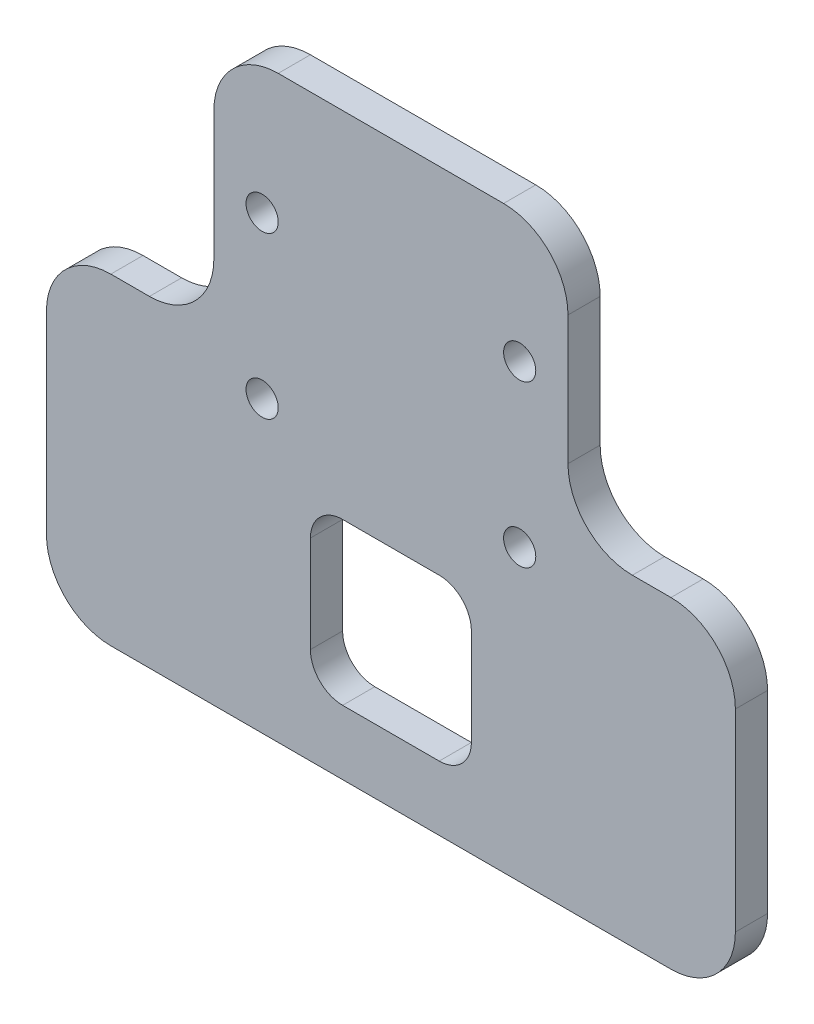
SolidWorks part; units mm, degrees
material "Maple"
ref_plane "Front Plane" through (0, 0, 0) normal (0, 0, 1) x (1, 0, 0)
ref_plane "Top Plane" through (0, 0, 0) normal (0, 1, 0) x (1, 0, 0)
ref_plane "Right Plane" through (0, 0, 0) normal (1, 0, 0) x (0, 0, -1)
sketch "Sketch1" plane through (0, 0, 0) normal (0, 0, 1) x (1, 0, 0)
  line L1 (-53.5, -25) -> (53.5, -25)
  line L2 (-53.5, -25) -> (-53.5, 25)
  line L3 (-53.5, 25) -> (53.5, 25) construction
  line L4 (53.5, -25) -> (53.5, 25)
  line L5 (-53.5, -25) -> (53.5, 25) construction
  line L6 (-53.5, 25) -> (53.5, -25) construction
  line L10 (0, 25) -> (0, -25) construction
  line L22 (-27.5, 65) -> (27.5, 65)
  line L23 (-27.5, 65) -> (-27.5, 25)
  line L24 (-27.5, 25) -> (27.5, 25) construction
  line L25 (27.5, 65) -> (27.5, 25)
  line L26 (-27.5, 65) -> (27.5, 25) construction
  line L27 (-27.5, 25) -> (27.5, 65) construction
  line L28 (53.5, 25) -> (27.5, 25)
  line L29 (-27.5, 25) -> (-53.5, 25)
  line L31 (-12.5, -15) -> (12.5, -15)
  line L32 (-12.5, -15) -> (-12.5, 10)
  line L33 (-12.5, 10) -> (12.5, 10)
  line L34 (12.5, -15) -> (12.5, 10)
  line L35 (-12.5, -15) -> (12.5, 10) construction
  line L36 (-12.5, 10) -> (12.5, -15) construction
  circle A5 centre (-38.5, 5) radius 4
  circle A6 centre (38.5, 5) radius 4
  circle A13 centre (-20, 45) radius 2.5
  circle A14 centre (-20, 20) radius 2.5
  circle A15 centre (20, 20) radius 2.5
  circle A16 centre (20, 45) radius 2.5
  point P0 (0, 0)
  point P7 (0, 45)
  point P17 (0, -2.5)
  dimension "D5" = 8
  dimension "D9" = 5
  dimension "D1" = 107
  dimension "D2" = 50
  dimension "D3" = 15
  dimension "D4" = 20
  dimension "D6" = 40
  dimension "D7" = 55
  dimension "D8" = 40
  dimension "D10" = 25
  dimension "D11" = 10
  dimension "D12" = 25
  dimension "D13" = 25
  dimension "D21" = 77
extrude "Boss-Extrude1" [suppressed] add sketch "Sketch1" along normal mid plane 5
fillet "Fillet1" [suppressed] radius 10
fillet "Fillet2" [suppressed] radius 1
extrude "Boss-Extrude2" add sketch "Sketch1<4>" along normal blind 5 contours L23 L29 L2 L1 L4 L28 L25 L22 A15 A14 A13 L34 L31 L32 L33 A5 A6 A16 | A5 | A6 region at (0, 14.4542, 0)
sketch "Sketch1<4>" plane through (0, 0, 0) normal (0, 0, 1) x (1, 0, 0) same geometry as "Sketch1"
fillet "Fillet3" radius 10 8 edges at (-27.5, 65, 2.5) (27.5, 65, 2.5) (27.5, 25, 2.5) (53.5, 25, 2.5) (53.5, -25, 2.5) (-53.5, 25, 2.5) (-27.5, 25, 2.5) (-53.5, -25, 2.5)
fillet "Fillet4" radius 5 4 edges at (-12.5, 10, 2.5) (-12.5, -15, 2.5) (12.5, -15, 2.5) (12.5, 10, 2.5)
